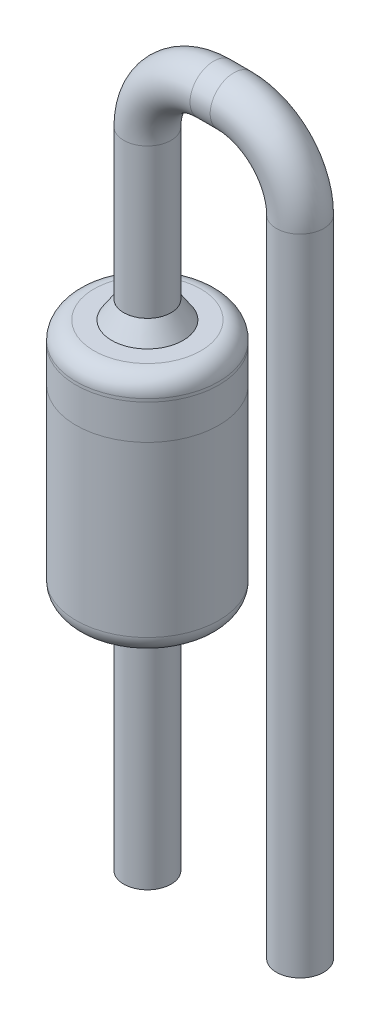
SolidWorks part; units mm, degrees
ref_plane "Front Plane" through (0, 0, 0) normal (0, 0, 1) x (1, 0, 0)
ref_plane "Top Plane" through (0, 0, 0) normal (0, 1, 0) x (1, 0, 0)
ref_plane "Right Plane" through (0, 0, 0) normal (1, 0, 0) x (0, 0, -1)
ref_plane "BODY_RPlane" through (0, 0, 0) normal (1, 0, 0) x (0, 0, -1)
sketch "Sketch10" plane through (0, 0, 0) normal (0, 0, 1) x (1, 0, 0)
  line L1 (-0.8906, 5.335) -> (-0.5938, 5.335)
  line L3 (0, 3.3175) -> (-1.1875, 3.3175) construction
  line L12 (-1.1875, 1.5969) -> (-1.1875, 5.0381)
  line L14 (-0.7076, 1.3) -> (-0.1163, 1.3) construction
  line L15 (-0.5938, 1.3) -> (-0.5938, 3.3175) construction
  line L16 (-0.8906, 1.3) -> (-0.5938, 1.3)
  line L17 (-0.5938, 1.3) -> (-0.5938, 5.335)
  line L18 (0, 1) -> (0, 5.635) construction
  arc A6 (-1.1875, 1.5969) -> (-0.8906, 1.3) centre (-0.8906, 1.5969) ccw
  arc A8 (-1.1875, 5.0381) -> (-0.8906, 5.335) centre (-0.8906, 5.0381) cw
  point P22 (0, 3.3175)
  point P30 (-1.1875, 3.3175)
  point P31 (-0.5938, 3.3175)
  point P34 (-1.1875, 3.3175)
  dimension "D8" = 0.2969
  dimension "D1" = 4.635
  dimension "D7" = 1.1875
  dimension "D9" = 0.3
  dimension "D10" = 0.5938
  dimension "D2" = 3.3175
revolve "BODY_main" add sketch "Sketch10" angle 360 about L18
sketch "Sketch11" plane through (0, 0, 0) normal (0, 0, 1) x (1, 0, 0)
  line L4 (0, 1.3) -> (0, 1)
  line L17 (-200000.7076, 1.3) -> (199999.8837, 1.3) construction
  line L18 (0, 1) -> (0, 5.635) construction
  line L19 (0, 1) -> (-0.3937, 1)
  line L20 (-0.3937, 1) -> (-0.5938, 1.3)
  line L21 (-0.5938, 1.3) -> (0, 1.3)
  line L22 (-1.1875, 3.3175) -> (0, 3.3175) construction
  line L23 (-0.5938, 5.335) -> (0, 5.335)
  line L24 (-0.3937, 5.635) -> (-0.5938, 5.335)
  line L25 (0, 5.635) -> (-0.3937, 5.635)
  line L26 (0, 5.335) -> (0, 5.635)
  dimension "D3" = 0.3937
revolve "BODY_to_PIN" add sketch "Sketch11" angle 360 about L18
ref_plane "TEXT_plane" through (-1.2875, 0, 0) normal (1, 0, 0) x (0, 0, -1)
sketch "Sketch4"
  dimension "D1" = 7.4613
  dimension "D3" = 0.5794
  dimension "D5" = 0.05
  dimension "D6" = 0.15
  dimension "D2" = 5
wrap "TEXT_Wrap" sketch "Sketch4" wrap type scribe source sketch "Sketch4" face at (1.1875, 1.5969, 0)
sketch "Sketch6" plane through (1, 1, 0) normal (0, 1, 0) x (0, 0, -1)
  circle A0 centre (0, 1) radius 0.3937
  dimension "D1" = 0.7875
sketch "Sketch7" plane through (0, 0, 0) normal (0, 0, 1) x (1, 0, 0)
  line L0 (1.4375, 9.2207) -> (1.1025, 9.2207)
  line L1 (0, 8.1182) -> (0, -2.6)
  line L2 (1.27, 9.2207) -> (1.27, -2.6) construction
  line L3 (0, -2.6) -> (1.27, -2.6) construction
  line L5 (0, 8.1182) -> (0, 5.635)
  line L6 (2.54, 8.1182) -> (2.54, -2.6)
  line L7 (0, -4.1102) -> (0, 4.1102) construction
  line L8 (0.3937, 5.635) -> (-0.3937, 5.635) construction
  arc A0 (1.1025, 9.2207) -> (0, 8.1182) centre (1.1025, 8.1182) ccw
  arc A1 (1.4375, 9.2207) -> (2.54, 8.1182) centre (1.4375, 8.1182) cw
  point P11 (0, 5.635)
  dimension "D3" = 1.1025
  dimension "D1" = 2.6
sweep "PINS" add profiles "Sketch6" path "Sketch7"
equation "\"D4@Sketch7\"=\"PIN_PITCH\""
equation "\"pin_config-----------------\"= 0x000000000000000000000000000000000"
equation "\"PIN_PITCH\"= 100mil"
equation "\"PCB_standoff\"= 1mm"
equation "\"PCB_thickness\"= 1.6mm"
equation "\"PCB_bottom_lead\"= 1.0mm"
equation "\"PIN_C_max\"= 0.863mm"
equation "\"PIN_C_min\"= 0.712mm"
equation "\"body_config----------------\"= 0x000000000000000000000000000000000"
equation "\"BODY_B_max\"= 5.2mm"
equation "\"BODY_B_min\"= 4.07mm"
equation "\"BODY_D_max\"= 2.71mm"
equation "\"BODY_D_min\"= 2.04mm"
equation "\"part_config----------------\"= 0x000000000000000000000000000000000"
equation "\"Component_Size\"= 1"
equation "\"Component_Type\"= 0'variable is not used"
equation "\"D1@TEXT_plane\"=\"BODY_D\"/2 + 0.1"
equation "\"D1@Sketch4\"=\"BODY_D\" * pi"
equation "\"D1@Sketch6\"=\"PIN_C\""
equation "\"D3@Sketch7\"=\"PIN_R\""
equation "\"D1@Sketch7\"=\"PIN_L\""
equation "\"D3@Sketch4\"=\"BODY_CATM_H1\""
equation "\"D1@Sketch10\"=\"BODY_B\""
equation "\"D7@Sketch10\"=\"BODY_D\"/2"
equation "\"D8@Sketch10\"=\"BODY_D\"/8"
equation "\"D10@Sketch10\"=\"BODY_D\"/4"
equation "\"D2@Sketch10\"=\"BODY_B\"/2 + \"PCB_standoff\""
equation "\"D3@Sketch11\"=\"PIN_C\"/2"
equation "\"PIN_A_min\"= 17mm"
equation "\"D2@Sketch7\"=\"PIN_A_min\""
equation "\"auto_calc-------------------\"= 0x000000000000000000000000000000000"
equation "\"BODY_B\"= IIF ( \"Component_Size\" > 0 , IIF ( \"Component_Size\" = 1 , ( ( \"BODY_B_max\" + \"BODY_B_min\" ) / 2 ) , \"BODY_B_max\" ) , \"BODY_B_min\" )'NOT_FOR_USER , AUTOMATIC CALCULATION"
equation "\"BODY_D\"= IIF ( \"Component_Size\" > 0 , IIF ( \"Component_Size\" = 1 , ( ( \"BODY_D_max\" + \"BODY_D_min\" ) / 2 ) , \"BODY_D_max\" ) , \"BODY_D_min\" )'NOT_FOR_USER , AUTOMATIC CALCULATION"
equation "\"PIN_C\"= IIF ( \"Component_Size\" > 0 , IIF ( \"Component_Size\" = 1 , ( ( \"PIN_C_max\" + \"PIN_C_min\" ) / 2 ) , \"PIN_C_max\" ) , \"PIN_C_min\" )'NOT_FOR_USER , AUTOMATIC CALCULATION"
equation "\"PIN_L\"= \"PCB_thickness\" + \"PCB_bottom_lead\"'NOT_FOR_USER , AUTOMATIC CALCULATION"
equation "\"PIN_R\"= \"PIN_C\" * 1.4'NOT_FOR_USER , AUTOMATIC CALCULATION"
equation "\"BODY_CATM_H1\"= \"BODY_B\" / 8'NOT_FOR_USER , AUTOMATIC CALCULATION"
